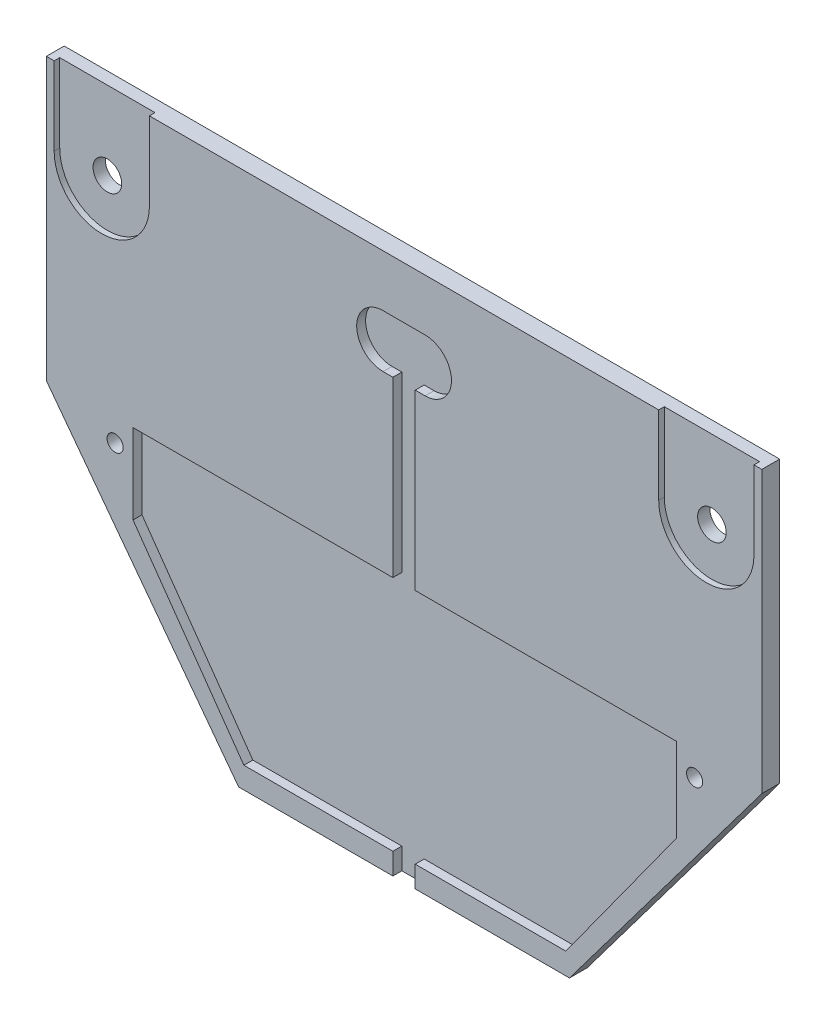
SolidWorks part; units mm, degrees
note: The reader was unsure of these and kept them because the rebuilt part matched: thickness of "Base-Flange1", "Sheet-Metal1", "Sheet-Metal3", "Sheet-Metal4", "Sheet-Metal5", "Sheet-Metal6", "Sheet-Metal8", "Sheet-Metal9", "Sheet-Metal10", "Sheet-Metal11".
ref_plane "Front Plane" through (0, 0, 0) normal (0, 0, 1) x (1, 0, 0)
ref_plane "Top Plane" through (0, 0, 0) normal (0, 1, 0) x (1, 0, 0)
ref_plane "Right Plane" through (0, 0, 0) normal (1, 0, 0) x (0, 0, -1)
sketch "Sketch1" plane through (0, 0, 0) normal (0, 0, 1) x (1, 0, 0)
  line L0 (0, 0) -> (46.99, 0)
  line L1 (46.99, 0) -> (101.6, 72.644)
  line L2 (101.6, 72.644) -> (101.6, 152.4)
  line L3 (101.6, 152.4) -> (-101.6, 152.4)
  line L4 (-101.6, 152.4) -> (-101.6, 72.644)
  line L5 (-101.6, 72.644) -> (-46.99, 0)
  line L6 (-46.99, 0) -> (0, 0)
  point P7 (0, 152.4)
  dimension "D1" = 93.98
  dimension "D2" = 79.756
  dimension "D3" = 203.2
  dimension "D4" = 152.4
  dimension "D5" = 79.756
base flange "Base-Flange1" sketch "Sketch1" thickness 5.08 reverse thickness direction no parameters "D1"=1
sketch "Sketch2" plane through (0, 0, 0) normal (0, 0, 1) x (1, 0, 0)
  line L0 (-5.969, 137.668) -> (5.969, 137.668)
  line L1 (5.969, 122.682) -> (-5.969, 122.682)
  line L6 (101.6, 152.4) -> (-101.6, 152.4) construction
  line L7 (101.6, 72.644) -> (101.6, 152.4) construction
  arc A0 (5.969, 137.668) -> (5.969, 122.682) centre (5.969, 130.175) cw
  arc A1 (-5.969, 122.682) -> (-5.969, 137.668) centre (-5.969, 130.175) cw
  point P5 (-13.462, 130.175)
  point P7 (13.462, 130.175)
  point P9 (0, 137.668)
  point P12 (0, 152.4)
  dimension "D3" = 14.732
  dimension "D1" = 26.924
  dimension "D2" = 14.986
  dimension "D4" = 88.138
extrude "Tail Connection" cut sketch "Sketch2" against normal blind 2.54 normal cut yes
sketch "Sketch4" plane through (0, 0, 0) normal (0, 0, 1) x (1, 0, 0)
  circle A0 centre (-85.852, 130.175) radius 4.064
  circle A1 centre (85.852, 130.175) radius 4.064
  arc A2 (-5.969, 137.668) -> (-5.969, 122.682) centre (-5.969, 130.175) ccw construction
  arc A5 (5.969, 122.682) -> (5.969, 137.668) centre (5.969, 130.175) ccw construction
  point P9 (-13.462, 130.175)
  point P14 (13.462, 130.175)
  dimension "D1" = 72.39
  dimension "D2" = 72.39
extrude "Tab Bolt Holes" cut sketch "Sketch4" against normal through all normal cut yes
sketch "Sketch5" plane through (0, 0, 0) normal (0, 0, 1) x (1, 0, 0)
  line L0 (-76.9736, 50.6725) -> (-76.9736, 73.4016)
  line L1 (-76.9736, 73.4016) -> (77.4388, 73.4016)
  line L2 (77.4388, 73.4016) -> (77.4388, 49.6794)
  line L3 (77.4388, 49.6794) -> (45.9526, 6.0916)
  line L4 (45.9526, 6.0916) -> (-45.4874, 6.0916)
  line L5 (-45.4874, 6.0916) -> (-76.9736, 50.6725)
  point P2 (0.2326, 73.4016)
  point P7 (0.2326, 6.0916)
  dimension "D1" = 67.31
  dimension "D2" = 91.44
  dimension "D3" = 6.096
  dimension "D4" = 24.638
extrude "Battery Cutout" cut sketch "Sketch5" against normal blind 2.54 normal cut yes
sketch "Sketch6" plane through (0, 0, 0) normal (0, 0, 1) x (1, 0, 0)
  line L0 (-5.969, 122.682) -> (5.969, 122.682) construction
  line L1 (-3.175, 122.682) -> (3.175, 122.682)
  line L2 (-3.175, 122.682) -> (-3.175, 73.4016)
  line L3 (-3.175, 73.4016) -> (3.175, 73.4016)
  line L4 (3.175, 122.682) -> (3.175, 73.4016)
  line L5 (77.4388, 73.4016) -> (-76.9736, 73.4016) construction
  line L6 (101.6, 152.4) -> (-101.6, 152.4) construction
  point P10 (0, 152.4)
  point P11 (0, 122.682)
  dimension "D1" = 6.35
extrude "Top Wire Connection" cut sketch "Sketch6" against normal blind 2.54 normal cut yes
sketch "Sketch7" plane through (0, 0, 0) normal (0, 0, 1) x (1, 0, 0)
  line L0 (-45.4874, 6.0916) -> (45.9526, 6.0916) construction
  line L1 (-3.175, 6.0916) -> (3.175, 6.0916)
  line L2 (-3.175, 6.0916) -> (-3.175, 0)
  line L3 (-3.175, 0) -> (3.175, 0)
  line L4 (3.175, 6.0916) -> (3.175, 0)
  line L5 (-46.99, 0) -> (46.99, 0) construction
  line L6 (3.175, 73.4016) -> (3.175, 122.682) construction
  point P11 (0, 0)
extrude "Bottom Wires" cut sketch "Sketch7" against normal blind 2.54 normal cut yes
sketch "Sketch8" plane through (0, 0, 0) normal (0, 0, 1) x (1, 0, 0)
  line L0 (-76.9736, 73.4016) -> (-76.9736, 50.6725) construction
  line L1 (101.6, 152.4) -> (-101.6, 152.4) construction
  line L2 (77.4388, 49.6794) -> (77.4388, 73.4016) construction
  circle A0 centre (-82.0536, 67.056) radius 2.286
  circle A1 centre (82.5188, 67.056) radius 2.286
  dimension "D1" = 5.08
  dimension "D2" = 85.344
  dimension "D3" = 85.344
  dimension "D4" = 5.08
extrude "Bottom Bolts" cut sketch "Sketch8" against normal through all normal cut yes
sketch "Sketch9" plane through (0, 0, 0) normal (0, 0, 1) x (1, 0, 0)
  line L0 (72.3265, 152.4) -> (72.3265, 130.175)
  line L1 (101.6, 152.4) -> (-101.6, 152.4) construction
  line L2 (99.3775, 130.175) -> (99.3775, 152.4)
  line L3 (99.3775, 152.4) -> (72.3265, 152.4)
  arc A0 (72.3265, 130.175) -> (99.3775, 130.175) centre (85.852, 130.175) ccw
  circle A1 centre (85.852, 130.175) radius 4.064 construction
  dimension "D1" = 27.051
extrude "Cut-Extrude10" cut sketch "Sketch9" against normal blind 1.5875 normal cut yes
mirror "Mirror1" about plane through (0, 0, 0) normal (1, 0, 0) of "Cut-Extrude10"
sketch "Bend-Lines1" [suppressed] plane through (0, 0, 0) normal (0, 1, 0) x (1, 0, 0)
sketch "Bounding-Box1" [suppressed] plane through (0, 0, 0) normal (0, 1, 0) x (1, 0, 0)
sheet metal parameters "Sheet-Metal1" thickness 5.08 parameters "D1"=1
flat pattern "Flat-Pattern1" [suppressed]
sketch "Bend-Lines2" plane through (0, 0, 0) normal (0, 1, 0) x (1, 0, 0)
sketch3d "Bounding-Box2" [suppressed]
  line L0 (-101.6, 0, 0) -> (101.6, 0, 0) construction
  line L1 (-101.6, 152.4, 0) -> (101.6, 152.4, 0) construction
  line L2 (-101.6, 0, 0) -> (-101.6, 152.4, 0) construction
  line L3 (101.6, 0, 0) -> (101.6, 152.4, 0) construction
sheet metal parameters "Sheet-Metal3" thickness 5.08 parameters "D1"=1, "D7"=6.35
flat pattern "Flat-Pattern1"
sketch "Bend-Lines2" plane through (0, 0, 0) normal (0, 1, 0) x (1, 0, 0)
sketch3d "Bounding-Box2" [suppressed]
  line L0 (-101.6, 0, 0) -> (101.6, 0, 0) construction
  line L1 (-101.6, 152.4, 0) -> (101.6, 152.4, 0) construction
  line L2 (-101.6, 0, 0) -> (-101.6, 152.4, 0) construction
  line L3 (101.6, 0, 0) -> (101.6, 152.4, 0) construction
sheet metal parameters "Sheet-Metal4" thickness 5.08 parameters "D1"=1, "D7"=6.35
flat pattern "Flat-Pattern1"
sketch "Bend-Lines2" plane through (0, 0, 0) normal (0, 1, 0) x (1, 0, 0)
sketch3d "Bounding-Box2" [suppressed]
  line L0 (-101.6, 0, 0) -> (101.6, 0, 0) construction
  line L1 (-101.6, 152.4, 0) -> (101.6, 152.4, 0) construction
  line L2 (-101.6, 0, 0) -> (-101.6, 152.4, 0) construction
  line L3 (101.6, 0, 0) -> (101.6, 152.4, 0) construction
sheet metal parameters "Sheet-Metal5" thickness 5.08 parameters "D1"=1, "D7"=6.35
flat pattern "Flat-Pattern1"
sketch "Bend-Lines2" plane through (0, 0, 0) normal (0, 1, 0) x (1, 0, 0)
sketch3d "Bounding-Box2" [suppressed]
  line L0 (-101.6, 0, 0) -> (101.6, 0, 0) construction
  line L1 (-101.6, 152.4, 0) -> (101.6, 152.4, 0) construction
  line L2 (-101.6, 0, 0) -> (-101.6, 152.4, 0) construction
  line L3 (101.6, 0, 0) -> (101.6, 152.4, 0) construction
sheet metal parameters "Sheet-Metal6" thickness 5.08 parameters "D1"=1, "D7"=6.35
flat pattern "Flat-Pattern1"
sketch "Bend-Lines2" plane through (0, 0, 0) normal (0, 1, 0) x (1, 0, 0)
sketch3d "Bounding-Box2" [suppressed]
  line L0 (-101.6, 0, 0) -> (101.6, 0, 0) construction
  line L1 (-101.6, 152.4, 0) -> (101.6, 152.4, 0) construction
  line L2 (-101.6, 0, 0) -> (-101.6, 152.4, 0) construction
  line L3 (101.6, 0, 0) -> (101.6, 152.4, 0) construction
sheet metal parameters "Sheet-Metal8" thickness 5.08 parameters "D1"=1, "D7"=6.35
flat pattern "Flat-Pattern1"
sketch "Bend-Lines2" plane through (0, 0, 0) normal (0, 1, 0) x (1, 0, 0)
sketch3d "Bounding-Box2" [suppressed]
  line L0 (-101.6, 0, 0) -> (101.6, 0, 0) construction
  line L1 (-101.6, 152.4, 0) -> (101.6, 152.4, 0) construction
  line L2 (-101.6, 0, 0) -> (-101.6, 152.4, 0) construction
  line L3 (101.6, 0, 0) -> (101.6, 152.4, 0) construction
sheet metal parameters "Sheet-Metal9" thickness 5.08 parameters "D1"=1, "D7"=6.35
flat pattern "Flat-Pattern1"
sketch "Bend-Lines2" plane through (0, 0, 0) normal (0, 1, 0) x (1, 0, 0)
sketch3d "Bounding-Box2" [suppressed]
  line L0 (-101.6, 0, 0) -> (101.6, 0, 0) construction
  line L1 (-101.6, 152.4, 0) -> (101.6, 152.4, 0) construction
  line L2 (-101.6, 0, 0) -> (-101.6, 152.4, 0) construction
  line L3 (101.6, 0, 0) -> (101.6, 152.4, 0) construction
sheet metal parameters "Sheet-Metal10" thickness 5.08 parameters "D1"=1, "D7"=6.35
flat pattern "Flat-Pattern1"
sketch "Bend-Lines2" plane through (0, 0, 0) normal (0, 1, 0) x (1, 0, 0)
sketch3d "Bounding-Box2" [suppressed]
  line L0 (-101.6, 0, 0) -> (101.6, 0, 0) construction
  line L1 (-101.6, 152.4, 0) -> (101.6, 152.4, 0) construction
  line L2 (-101.6, 0, 0) -> (-101.6, 152.4, 0) construction
  line L3 (101.6, 0, 0) -> (101.6, 152.4, 0) construction
sheet metal parameters "Sheet-Metal11" thickness 5.08 parameters "D1"=1, "D7"=6.35
flat pattern "Flat-Pattern1"
sketch "Bend-Lines2" plane through (0, 0, 0) normal (0, 1, 0) x (1, 0, 0)
sketch3d "Bounding-Box2" [suppressed]
  line L0 (-101.6, 0, 0) -> (101.6, 0, 0) construction
  line L1 (-101.6, 152.4, 0) -> (101.6, 152.4, 0) construction
  line L2 (-101.6, 0, 0) -> (-101.6, 152.4, 0) construction
  line L3 (101.6, 0, 0) -> (101.6, 152.4, 0) construction
